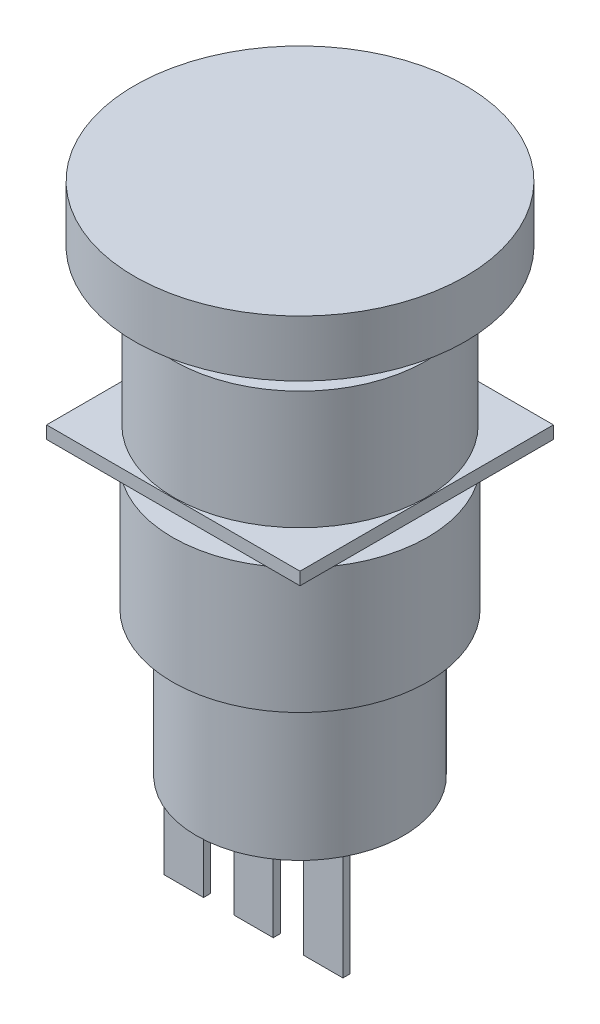
SolidWorks part; units mm, degrees
ref_plane "Plano frontal" through (0, 0, 0) normal (0, 0, 1) x (1, 0, 0)
ref_plane "Plano superior" through (0, 0, 0) normal (0, 1, 0) x (1, 0, 0)
ref_plane "Plano direito" through (0, 0, 0) normal (1, 0, 0) x (0, 0, -1)
sketch "Esboço1" plane through (0, 0, 0) normal (0, 0, 1) x (1, 0, 0)
  line L0 (0, 0) -> (0, -30) construction
  line L1 (0, 0) -> (-8.95, 0)
  line L2 (-8.95, 0) -> (-8.95, -8.4)
  line L3 (-8.95, -8.4) -> (-7.35, -8.4)
  line L4 (-7.35, -8.4) -> (-7.35, -30)
  line L5 (-7.35, -30) -> (0, -30)
  line L6 (0, 0) -> (0, -30)
  dimension "D1" = 30
  dimension "D2" = 8.4
  dimension "D3" = 17.9
  dimension "D4" = 14.7
revolve "Revolução1" add sketch "Esboço1" angle 360 about L0
sketch "Esboço2" plane through (0, -8.4, 0) normal (0, -1, 0) x (1, 0, 0)
  line L1 (9, -9) -> (-9, -9)
  line L2 (9, -9) -> (9, 9)
  line L3 (9, 9) -> (-9, 9)
  line L4 (-9, -9) -> (-9, 9)
  line L5 (9, -9) -> (-9, 9) construction
  line L6 (9, 9) -> (-9, -9) construction
  point P0 (0, 0)
  dimension "D1" = 18
extrude "Ressalto-extrusão1" add sketch "Esboço2" along normal blind 0.9
sketch "Esboço3" plane through (0, 0, 0) normal (0, 0, 1) x (1, 0, 0)
  line L0 (0, 0) -> (0, -3.8) construction
  line L1 (-11.75, 6.6) -> (-11.75, 2.6)
  line L2 (-11.75, 2.6) -> (-7.8, 2.6)
  line L3 (-7.8, 2.6) -> (-7.8, -3.8)
  line L4 (-7.8, -3.8) -> (0, -3.8)
  line L5 (-11.75, 6.6) -> (0, 6.6)
  line L6 (0, 6.6) -> (0, 0) construction
  line L7 (-7.35, -30) -> (7.35, -30) construction
  line L8 (0, -3.8) -> (0, 6.6)
  dimension "D1" = 23.5
  dimension "D2" = 4
  dimension "D3" = 10.4
  dimension "D4" = 15.6
  dimension "D5" = 36.6
revolve "Revolução2" add sketch "Esboço3" angle 360 about L8
sketch "Esboço4" plane through (0, 0, 0) normal (0, 0, 1) x (1, 0, 0)
  line L0 (-7.35, -30) -> (7.35, -30) construction
  line L1 (-6.35, -30) -> (-3.55, -30)
  line L2 (-6.35, -30) -> (-6.35, -37.6)
  line L3 (-6.35, -37.6) -> (-3.55, -37.6)
  line L4 (-3.55, -30) -> (-3.55, -37.6)
  line L5 (0, -30) -> (0, 0) construction
  line L6 (-1.4, -30) -> (1.4, -30)
  line L7 (-1.4, -30) -> (-1.4, -37.6)
  line L8 (-1.4, -37.6) -> (1.4, -37.6)
  line L9 (1.4, -30) -> (1.4, -37.6)
  line L10 (3.55, -30) -> (6.35, -30)
  line L11 (3.55, -30) -> (3.55, -37.6)
  line L12 (3.55, -37.6) -> (6.35, -37.6)
  line L13 (6.35, -30) -> (6.35, -37.6)
  line L14 (-3.55, -37.6) -> (-1.4, -37.6) construction
  line L15 (1.4, -37.6) -> (3.55, -37.6) construction
  dimension "D1" = 2.8
  dimension "D2" = 7.6
  dimension "D3" = 12.7
extrude "Ressalto-extrusão2" add sketch "Esboço4" along normal blind 0.5 from offset 2.8
sketch "Esboço5" plane through (0, 0, 0) normal (0, 0, 1) x (1, 0, 0)
  line L0 (-9.05, -10.8) -> (-9.05, -19.7)
  line L1 (-9.05, -19.7) -> (-7.45, -19.7)
  line L2 (-7.45, -19.7) -> (-7.45, -10.8)
  line L3 (-7.45, -10.8) -> (-9.05, -10.8)
  line L4 (0, 0) -> (0, -43.6299) construction
  line L5 (9, -9.3) -> (-9, -9.3) construction
  dimension "D1" = 18.1
  dimension "D2" = 1.6
  dimension "D3" = 8.9
  dimension "D4" = 1.5
revolve "Revolução3" add sketch "Esboço5" angle 360 about L4
sketch "Esboço6" [suppressed] plane through (0, 9.4, 0) normal (0, 1, 0) x (1, 0, 0)
  circle A0 centre (0, 0) radius 7.8 construction
  circle A1 centre (0, 0) radius 7.8
  circle A2 centre (0, 0) radius 11.75 construction
  circle A3 centre (0, 0) radius 11.75
extrude "Corte-extrusão1" [suppressed] cut sketch "Esboço6" against normal up to surface (4 mm away) up to face at (7.8, 2.6, 0)
